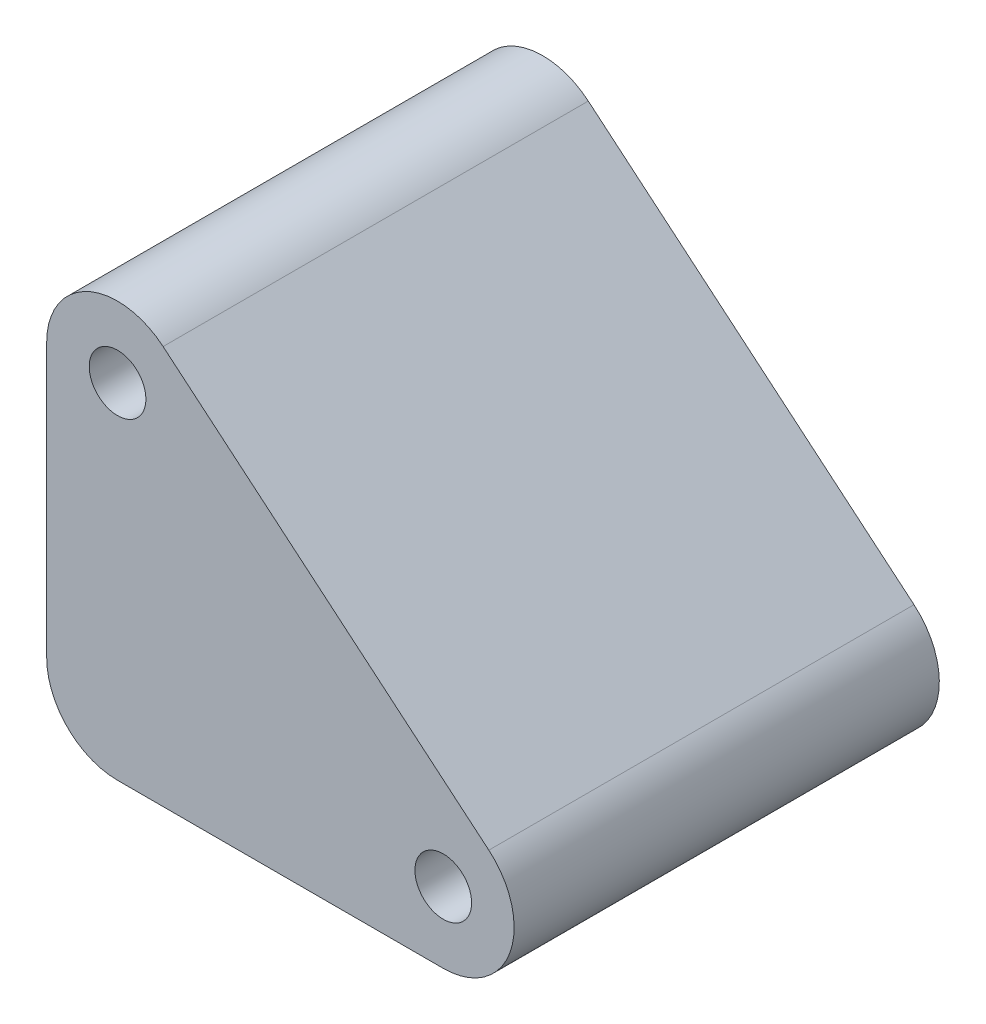
SolidWorks part; units mm, degrees
ref_plane "Front Plane" through (0, 0, 0) normal (0, 0, 1) x (1, 0, 0)
ref_plane "Top Plane" through (0, 0, 0) normal (0, 1, 0) x (1, 0, 0)
ref_plane "Right Plane" through (0, 0, 0) normal (1, 0, 0) x (0, 0, -1)
sketch "Sketch1" plane through (0, 0, 0) normal (0, 0, 1) x (1, 0, 0)
  line L0 (-201.8919, 158.1745) -> (-178.9105, 138.8909)
  line L1 (-182.1245, 130.0606) -> (-205.1058, 130.0606)
  line L2 (-210.1058, 135.0606) -> (-210.1058, 154.3443)
  circle A0 centre (-182.1245, 135.0606) radius 2 construction
  circle A1 centre (-205.1058, 154.3443) radius 2 construction
  circle A2 centre (-182.1245, 135.0606) radius 2
  circle A3 centre (-205.1058, 154.3443) radius 2
  arc A4 (-178.9105, 138.8909) -> (-182.1245, 130.0606) centre (-182.1245, 135.0606) cw
  arc A5 (-205.1058, 130.0606) -> (-210.1058, 135.0606) centre (-205.1058, 135.0606) cw
  arc A6 (-210.1058, 154.3443) -> (-201.8919, 158.1745) centre (-205.1058, 154.3443) cw
  dimension "D1" = 5
  dimension "D2" = 5
  dimension "D3" = 5
extrude "Boss-Extrude1" add sketch "Sketch1" along normal blind 15 and the other way blind 15
